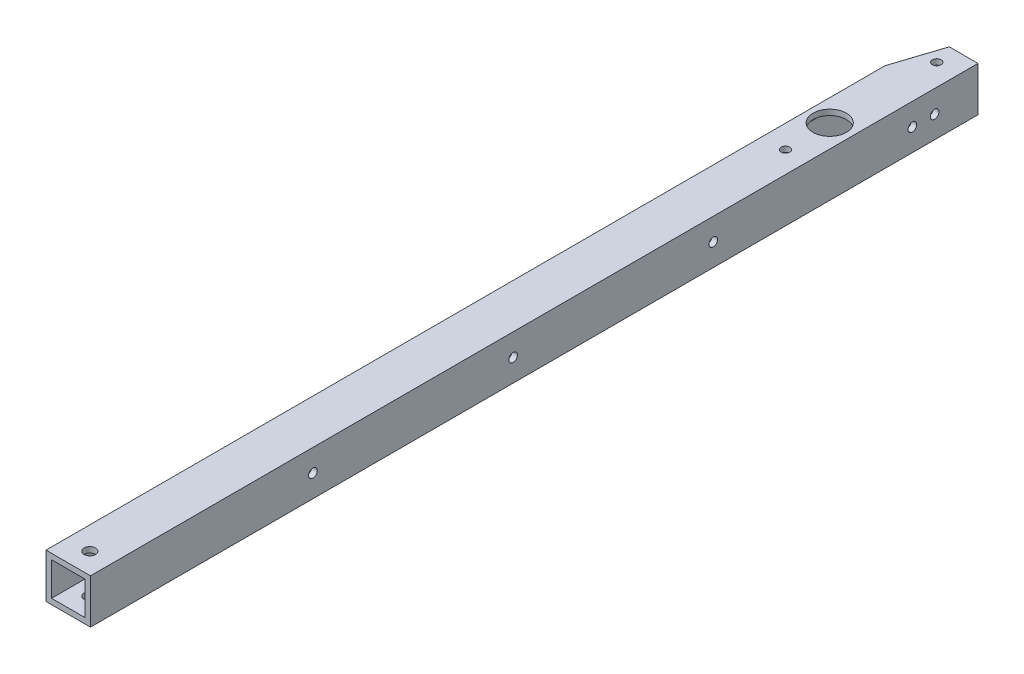
SolidWorks part; units mm, degrees
material "6061 Alloy"
ref_plane "Front Plane" through (0, 0, 0) normal (0, 0, 1) x (1, 0, 0)
ref_plane "Top Plane" through (0, 0, 0) normal (0, 1, 0) x (1, 0, 0)
ref_plane "Right Plane" through (0, 0, 0) normal (1, 0, 0) x (0, 0, -1)
sketch "Sketch1" plane through (0, 0, 0) normal (0, 0, 1) x (1, 0, 0)
  line L0 (-9.525, 9.525) -> (9.525, 9.525)
  line L2 (-12.7, 12.7) -> (12.7, 12.7)
  line L3 (-12.7, 12.7) -> (-12.7, -12.7)
  line L4 (-12.7, -12.7) -> (12.7, -12.7)
  line L5 (12.7, 12.7) -> (12.7, -12.7)
  line L10 (9.525, 9.525) -> (9.525, -9.525)
  line L11 (-9.525, -9.525) -> (9.525, -9.525)
  line L12 (-9.525, 9.525) -> (-9.525, -9.525)
  point P12 (0, 12.7)
  point P14 (12.7, 0)
  dimension "Wall Thickness" = 3.175
  dimension "Outside Width" = 25.4
  dimension "Outside Height" = 25.4
  dimension "Inside Height" = 19.05
  dimension "Inside Width" = 19.05
sketch "Sketch2" plane through (0, 0, 0) normal (1, 0, 0) x (0, 0, -1)
  line L0 (260.35, 0) -> (-260.35, 0)
  point P4 (0, 0)
  point P7 (-260.35, 0)
  point P10 (260.35, 0)
  dimension "Length" = 520.7
sketch "Sketch3" plane through (0, 0, 0) normal (0, 0, 1) x (1, 0, 0)
  line L21 (12.7, 12.7) -> (-12.7, 12.7)
  line L22 (12.7, -12.7) -> (12.7, 12.7)
  line L23 (-12.7, -12.7) -> (12.7, -12.7)
  line L24 (-12.7, 12.7) -> (-12.7, -12.7)
  line L25 (12.7, 12.7) -> (-12.7, 12.7)
  line L26 (12.7, -12.7) -> (12.7, 12.7)
  line L27 (-12.7, -12.7) -> (12.7, -12.7)
  line L28 (-12.7, 12.7) -> (-12.7, -12.7)
  line L29 (9.525, 9.525) -> (-9.525, 9.525)
  line L30 (9.525, -9.525) -> (9.525, 9.525)
  line L31 (-9.525, -9.525) -> (9.525, -9.525)
  line L32 (-9.525, 9.525) -> (-9.525, -9.525)
  line L33 (9.525, 9.525) -> (-9.525, 9.525)
  line L34 (9.525, -9.525) -> (9.525, 9.525)
  line L35 (-9.525, -9.525) -> (9.525, -9.525)
  line L36 (-9.525, 9.525) -> (-9.525, -9.525)
  dimension "D1" = 0
  dimension "D2" = 0
extrude "Boss-Extrude1" add sketch "Sketch3" along normal up to vertex (260.35 mm away) and the other way up to vertex (260.35 mm away) up to point (0, 0, 260.35) other way up to point (0, 0, -260.35)
sketch "Drawing Reference" plane through (0, 0, 0) normal (1, 0, 0) x (0, 0, -1)
  line L0 (-260.35, 0) -> (260.35, 0) construction
  line L1 (0, -12.7) -> (0, 12.7) construction
  line L2 (-260.35, -12.7) -> (260.35, -12.7) construction
  line L5 (-260.35, 12.7) -> (260.35, 12.7) construction
  point P7 (-242.062, 0)
  point P8 (242.062, 0)
  dimension "D1" = 18.288
sketch "Sketch4" plane through (0, 12.7, 0) normal (0, 1, 0) x (1, 0, 0)
  line L7 (-12.7, 218.6635) -> (-12.7, 260.35)
  line L10 (-12.7, -260.35) -> (-12.7, 260.35) construction
  line L11 (-12.7, 260.35) -> (12.7, 260.35)
  line L12 (12.7, 260.35) -> (12.7, 246.38)
  line L13 (12.7, -260.35) -> (12.7, 260.35) construction
  line L14 (12.7, 246.38) -> (-3.6932, 246.38)
  line L15 (-3.6932, 246.38) -> (-12.7, 218.6635)
  dimension "D1" = 13.97
  dimension "D2" = 41.6865
  dimension "D3" = 9.0068
extrude "Cut-Extrude1" cut sketch "Sketch4" against normal blind 25.4
sketch "Sketch5" plane through (0, 12.7, 0) normal (0, -1, 0) x (1, 0, 0)
  circle A0 centre (-0.2787, -174.7012) radius 9.525
  point P3 (-0.2787, -174.7012)
extrude "Cut-Extrude2" cut sketch "Sketch5" along normal blind 3.175
sketch "Sketch6" plane through (12.7, 0, 0) normal (1, 0, 0) x (0, 0, -1)
  line L0 (246.38, 0) -> (208.915, 0) construction
  line L1 (246.38, -12.7) -> (246.38, 12.7) construction
  line L2 (208.915, 0) -> (227.965, 0) construction
  dimension "D1" = 37.465
hole_wizard "#10 Clearance Hole2" positions "Sketch9" profile "Sketch10" hole size "#10" standard "ANSI Inch" end condition through all
sketch "Sketch9" plane through (0, -12.7, 0) normal (0, -1, 0) x (-1, 0, 0)
  point P0 (-0.379, 148.7845)
  point P3 (-0.3824, 235.171)
sketch "Sketch10" plane through (0.379, -12.7, -148.7845) normal (1, 0, 0) x (0, 0, -1)
  line L0 (0, 0) -> (0, 25.4)
  line L1 (0, 25.4) -> (2.4892, 25.4)
  line L2 (2.4892, 25.4) -> (2.4892, 0)
  line L5 (2.4892, 0) -> (0, 0)
  line L11 (0, -6.35) -> (0, 107.95) construction
  dimension "Thru Hole Dia." = 4.9784
  dimension "Thru Hole Depth" = 25.4
sketch "Sketch15" plane through (0, -12.7, 0) normal (0, -1, 0) x (1, 0, 0)
  line L0 (0.3633, 248.3836) -> (0.3633, 260.35) construction
  line L1 (-12.7, 260.35) -> (12.7, 260.35) construction
  circle A0 centre (0.3633, 248.3836) radius 3.175 construction
  point P2 (0, 260.35)
  dimension "D1" = 11.9664
  dimension "D2" = 0.3633
hole_wizard "1/4 Clearance Hole1" positions "Sketch11" profile "Sketch12" hole size "1/4" standard "ANSI Inch" end condition through all
sketch "Sketch11" plane through (0, -12.7, 0) normal (0, -1, 0) x (-1, 0, 0)
  point P0 (-0.3633, -248.3836)
sketch "Sketch12" plane through (0.3633, -12.7, 248.3836) normal (1, 0, 0) x (0, 0, -1)
  line L0 (0, 0) -> (0, 25.4)
  line L1 (0, 25.4) -> (3.2639, 25.4)
  line L2 (3.2639, 25.4) -> (3.2639, 0)
  line L5 (3.2639, 0) -> (0, 0)
  line L11 (0, -6.35) -> (0, 107.95) construction
  dimension "Thru Hole Dia." = 6.5278
  dimension "Thru Hole Depth" = 25.4
hole_wizard "#10 Clearance Hole3" positions "Sketch13" profile "Sketch14" hole size "#10" standard "ANSI Inch"
sketch "Sketch13" plane through (12.7, 0, 0) normal (1, 0, 0) x (0, 0, -1)
  point P0 (221.6129, -0.0596)
  point P4 (208.915, 0)
sketch "Sketch14" plane through (12.7, -0.0596, -221.6129) normal (0, 1, 0) x (0, 0, -1)
  line L0 (0, 0) -> (0, 6.5757)
  line L1 (0, 6.5757) -> (2.4892, 5.08)
  line L2 (2.4892, 5.08) -> (2.4892, 0)
  line L5 (2.4892, 0) -> (0, 0)
  line L10 (0, 6.5757) -> (-2.4892, 5.08) construction
  line L11 (0, -6.35) -> (0, 107.95) construction
  dimension "Hole Dia." = 4.9784
  dimension "Hole Depth" = 5.08
  dimension "Drill Angle" = 118
sketch "Sketch16" plane through (12.7, 0, 0) normal (1, 0, 0) x (0, 0, -1)
  line L0 (-260.35, 0) -> (-133.35, 0) construction
  line L1 (-260.35, -12.7) -> (-260.35, 12.7) construction
  line L2 (-133.35, 0) -> (-19.05, 0) construction
  line L3 (-19.05, 0) -> (95.25, 0) construction
  dimension "D1" = 127
  dimension "D2" = 114.3
  dimension "D3" = 114.3
hole_wizard "#10 Clearance Hole4" positions "Sketch17" profile "Sketch18" hole size "#10" standard "ANSI Inch" end condition through all
sketch "Sketch17" plane through (12.7, 0, 0) normal (1, 0, 0) x (0, 0, -1)
  point P0 (-133.35, 0)
  point P3 (-19.05, 0)
  point P6 (95.25, 0)
sketch "Sketch18" plane through (12.7, 0, 133.35) normal (0, 1, 0) x (0, 0, -1)
  line L0 (0, 0) -> (0, 25.4)
  line L1 (0, 25.4) -> (2.4892, 25.4)
  line L2 (2.4892, 25.4) -> (2.4892, 0)
  line L5 (2.4892, 0) -> (0, 0)
  line L11 (0, -6.35) -> (0, 107.95) construction
  dimension "Thru Hole Dia." = 4.9784
  dimension "Thru Hole Depth" = 25.4
equation "\"D1@Drawing Reference\"=\"Outside Width@Sketch1\" * 0.72"
